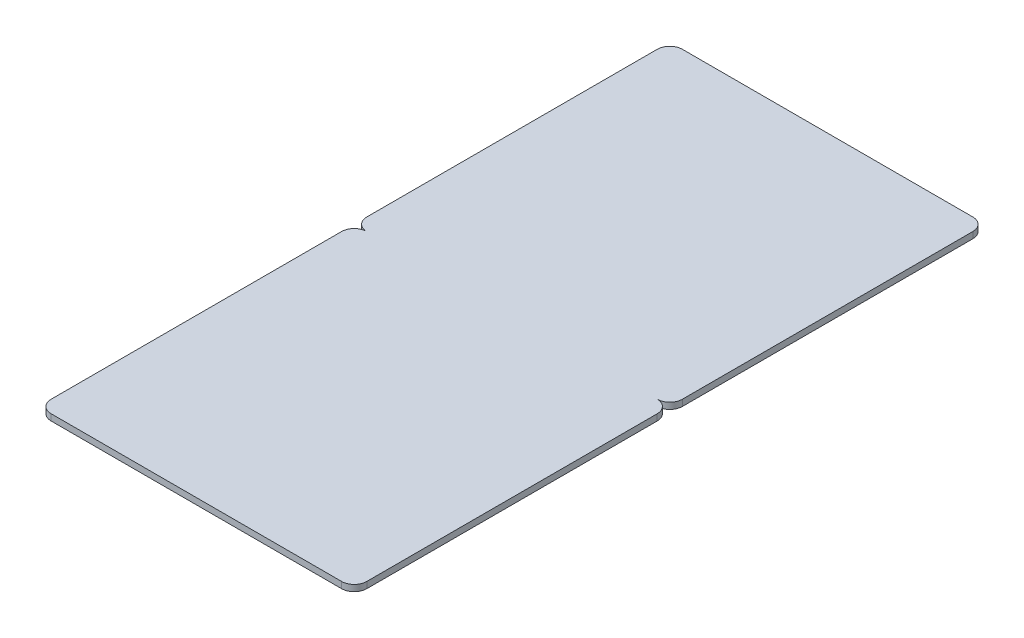
SolidWorks part; units mm, degrees
ref_plane "前视基准面" through (0, 0, 0) normal (0, 0, 1) x (1, 0, 0)
ref_plane "上视基准面" through (0, 0, 0) normal (0, 1, 0) x (1, 0, 0)
ref_plane "右视基准面" through (0, 0, 0) normal (1, 0, 0) x (0, 0, -1)
sketch "草图1" plane through (0, 0, 0) normal (0, 1, 0) x (1, 0, 0)
  line L1 (-11.5, 0) -> (11.5, 0)
  line L2 (-12.5, 1) -> (-12.5, 24)
  line L3 (-11.5, 25) -> (11.5, 25)
  line L4 (12.5, 1) -> (12.5, 24)
  line L5 (-12.5, 0) -> (12.5, 25) construction
  line L6 (-12.5, 25) -> (12.5, 0) construction
  arc A1 (-12.5, 24) -> (-11.5, 25) centre (-11.5, 24) cw
  arc A2 (12.5, 24) -> (11.5, 25) centre (11.5, 24) ccw
  arc A4 (-11.5, 0) -> (-12.5, 1) centre (-11.5, 1) cw
  arc A7 (11.5, 0) -> (12.5, 1) centre (11.5, 1) ccw
  point P0 (0, 12.5)
  dimension "D5" = 1
  dimension "D7" = 1
  dimension "D1" = 25
  dimension "D2" = 12.5
extrude "凸台-拉伸1" add sketch "草图1" along normal blind 0.5
ref_axis "基准轴2" through (0, 0, 0) along (1, 0, 0)
ref_axis "基准轴1" through (0, 0, 0) along (0, 1, 0)
pattern_circular "阵列(圆周)1" count 2 over 360 about axis through (0, 0, 0) along (0, 1, 0) of bodies 106 107
combine bodies "组合1" operation type add bodies to combine 106 108
